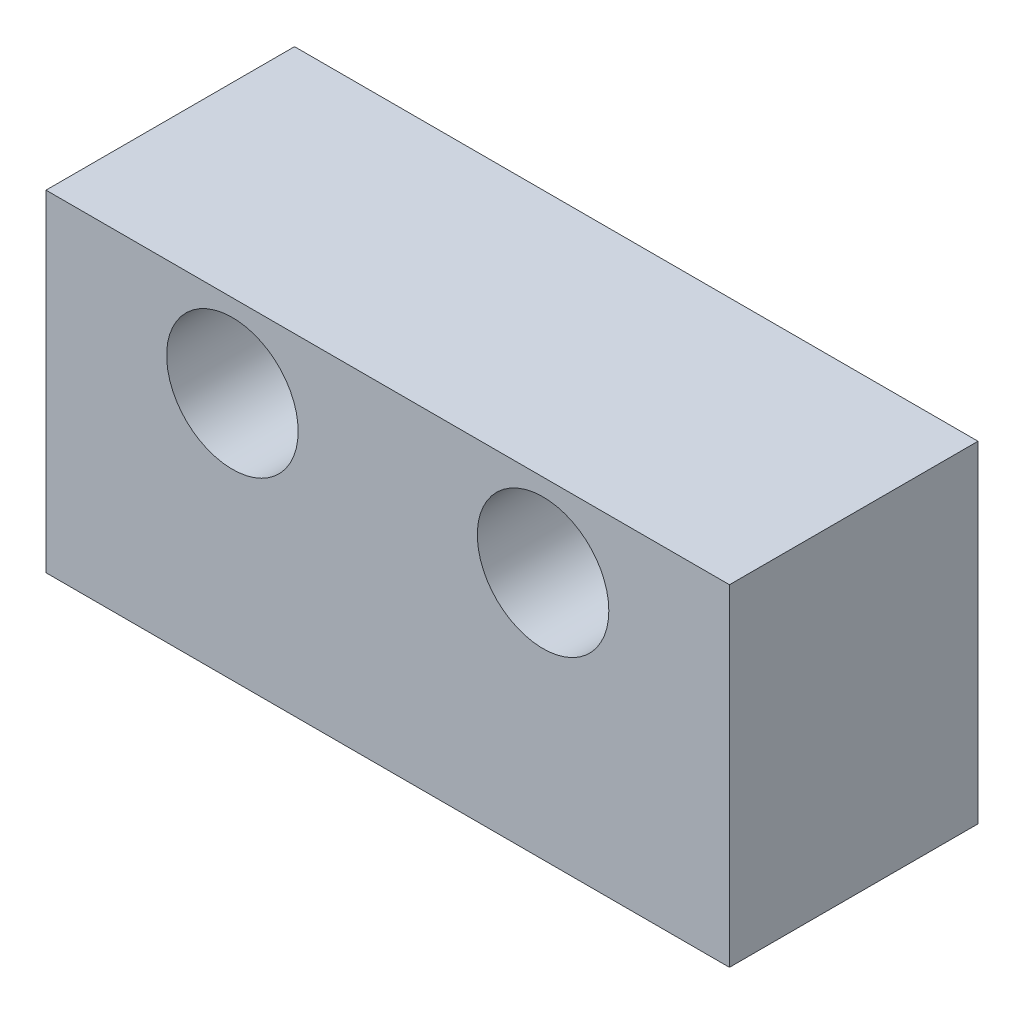
SolidWorks part; units mm, degrees
material "Plain Carbon Steel"
ref_plane "Front Plane" through (0, 0, 0) normal (0, 0, 1) x (1, 0, 0)
ref_plane "Top Plane" through (0, 0, 0) normal (0, 1, 0) x (1, 0, 0)
ref_plane "Right Plane" through (0, 0, 0) normal (1, 0, 0) x (0, 0, -1)
sketch "Sketch1" plane through (0, 0, 0) normal (0, 0, 1) x (1, 0, 0)
  line L0 (-16.5, -12) -> (16.5, -12)
  line L1 (16.5, -12) -> (16.5, 4)
  line L2 (16.5, 4) -> (-16.5, 4)
  line L3 (-16.5, 4) -> (-16.5, -12)
  circle A0 centre (7.5, 0) radius 3.175
  circle A1 centre (-7.5, 0) radius 3.175
  dimension "D1" = 6.35
  dimension "D2" = 6.35
extrude "Boss-Extrude1" add sketch "Sketch1" along normal blind 12
